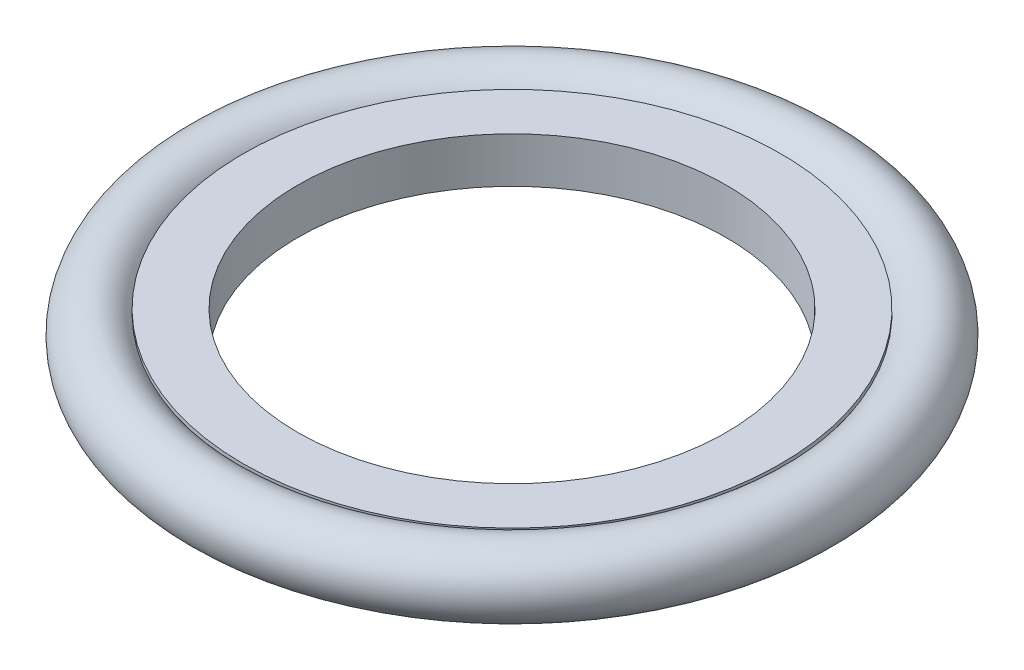
SolidWorks part; units mm, degrees
ref_plane "Front Plane" through (0, 0, 0) normal (0, 0, 1) x (1, 0, 0)
ref_plane "Top Plane" through (0, 0, 0) normal (0, 1, 0) x (1, 0, 0)
ref_plane "Right Plane" through (0, 0, 0) normal (1, 0, 0) x (0, 0, -1)
sketch "Sketch2" plane through (0, 0, 0) normal (1, 0, 0) x (0, 0, -1)
  line L0 (0, 0) -> (209.55, 0) construction
  line L1 (139.7, 0) -> (-139.7, 0) construction
  line L2 (209.55, 0) -> (254, 0) construction
  line L3 (209.55, 17.4625) -> (209.55, -17.4625) construction
  line L4 (0, 0) -> (0, -50000) construction
  circle A0 centre (228.3449, 0) radius 25.6551
  point P8 (209.55, 0)
  dimension "D4" = 51.3103
  dimension "D1" = 209.55
  dimension "D2" = 254
  dimension "D3" = 34.925
revolve "Revolve2" add sketch "Sketch2" angle 360 about L4
sketch "Sketch3" plane through (0, 0, 0) normal (1, 0, 0) x (0, 0, -1)
  line L0 (228.3449, 0) -> (50228.3449, 0) construction
  line L9 (209.6092, 17.526) -> (209.6092, -17.526) construction
  line L10 (207.0791, 17.526) -> (207.0791, 14.351)
  line L11 (207.0791, 14.351) -> (168.3342, 14.351)
  line L12 (168.3342, 14.351) -> (168.3342, -14.351)
  line L13 (207.0791, 17.526) -> (165.1592, 17.526)
  line L14 (165.1592, 17.526) -> (165.1592, -17.526)
  line L15 (207.0791, -17.526) -> (165.1592, -17.526)
  line L16 (207.0791, -14.351) -> (168.3342, -14.351)
  line L17 (207.0791, -17.526) -> (207.0791, -14.351)
  line L18 (0, 0) -> (0, -50000) construction
  circle A1 centre (228.3449, 0) radius 25.6551
  circle A2 centre (228.3449, 0) radius 25.6551 construction
  point P16 (165.1592, 0)
  point P18 (168.3342, 0)
  dimension "D2" = 35.052
  dimension "D3" = 3.175
  dimension "D4" = 3.175
  dimension "D5" = 44.45
  dimension "D1" = 0
revolve "Revolve3" add sketch "Sketch3" angle 360 about L18 other way angle 360
